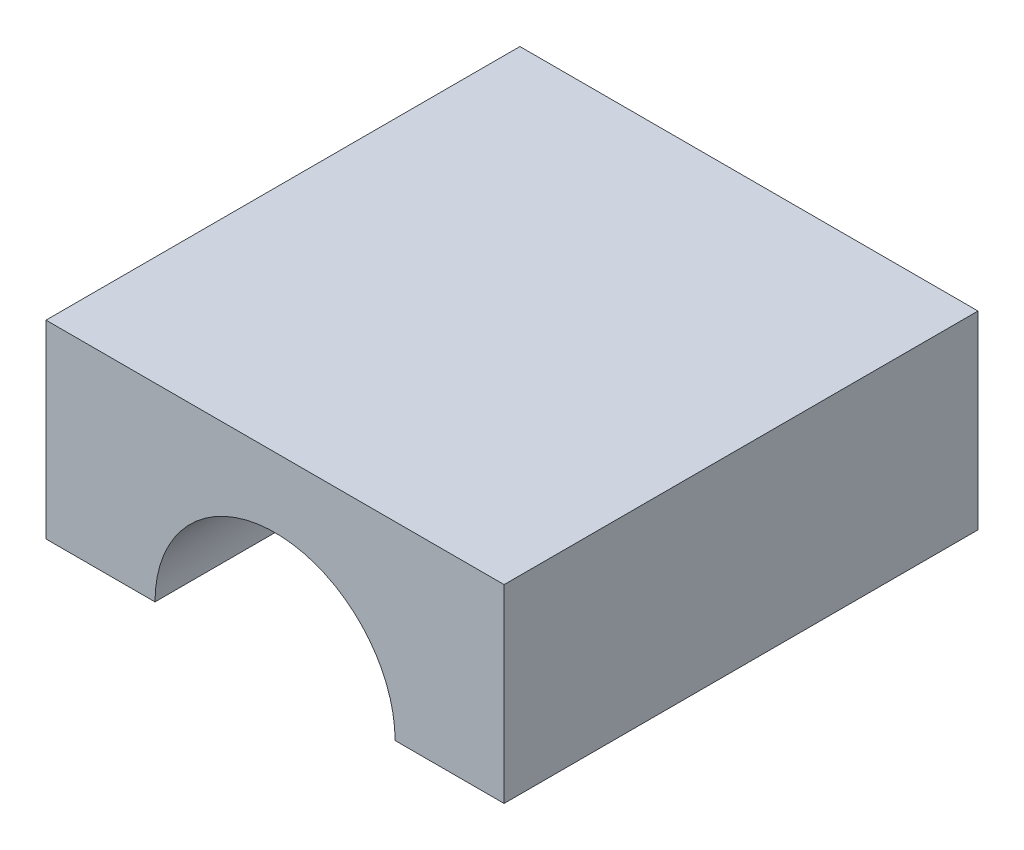
SolidWorks part; units mm, degrees
ref_plane "Front Plane" through (0, 0, 0) normal (1, 0, 0) x (0, 1, 0)
ref_plane "Top Plane" through (0, 0, 0) normal (0, 0, 1) x (0, 1, 0)
ref_plane "Right Plane" through (0, 0, 0) normal (0, 1, 0) x (-1, 0, 0)
sketch "Sketch1" plane through (0, 0, 0) normal (0, 0, 1) x (0, 1, 0)
  line L0 (0, -6.9) -> (0, -14.5) construction
  line L1 (0, 0) -> (12, 0)
  line L2 (0, 0) -> (0, -6.9)
  line L3 (0, -29) -> (12, -29)
  line L4 (12, 0) -> (12, -29)
  line L5 (6, -29) -> (6, 0) construction
  line L6 (0, -14.5) -> (12, -14.5) construction
  line L7 (0, -22.1) -> (0, -29)
  line L8 (0, -14.5) -> (0, -22.1) construction
  arc A0 (0, -22.1) -> (0, -6.9) centre (0, -14.5) ccw
  arc A1 (0, -6.9) -> (0, -22.1) centre (0, -14.5) ccw construction
  point P428 (6, -14.5)
  dimension "D3" = 15.2
  dimension "D1" = 29
  dimension "D2" = 12
extrude "Boss-Extrude1" add sketch "Sketch1" along normal blind 15 and the other way blind 15 contours A0 L7 L3 L4 L1 L2 region at (0.3138, 6, 0)
sketch "Sketch3" plane through (0, 12, 0) normal (0, 1, 0) x (-1, 0, 0)
  line L0 (0, 0) -> (-29, 0) construction
  line L1 (0, -15) -> (0, 15) construction
  line L2 (-29, -15) -> (-29, 15) construction
  line L3 (8, 0) -> (-37, 0) construction
  line L4 (8, -7) -> (-37, -7)
  line L5 (8, 7) -> (-37, 7)
  line L6 (-14.5, 15) -> (-14.5, -15) construction
  line L7 (0, 15) -> (-29, 15) construction
  line L8 (0, -15) -> (-29, -15) construction
  arc A0 (8, -7) -> (8, 7) centre (8, 0) ccw
  arc A1 (-37, 7) -> (-37, -7) centre (-37, 0) ccw
  circle A2 centre (-37, 0) radius 4
  circle A3 centre (8, 0) radius 4
  point P9 (-14.5, 0)
  point P22 (-14.5, 0)
  point P23 (4.0257, 0)
  point P26 (6.0767, -5.5403)
  point P27 (5.835, 0)
  point P28 (-59.3334, 1.6416)
  point P29 (6.8977, 0)
  point P30 (7.4638, -7)
  point P31 (0, 0)
  dimension "D3" = 8
  dimension "D1" = 3
  dimension "D2" = 3
  dimension "D4" = 45
equation "\"D2@Sketch3\"=\"D1@Sketch3\""
